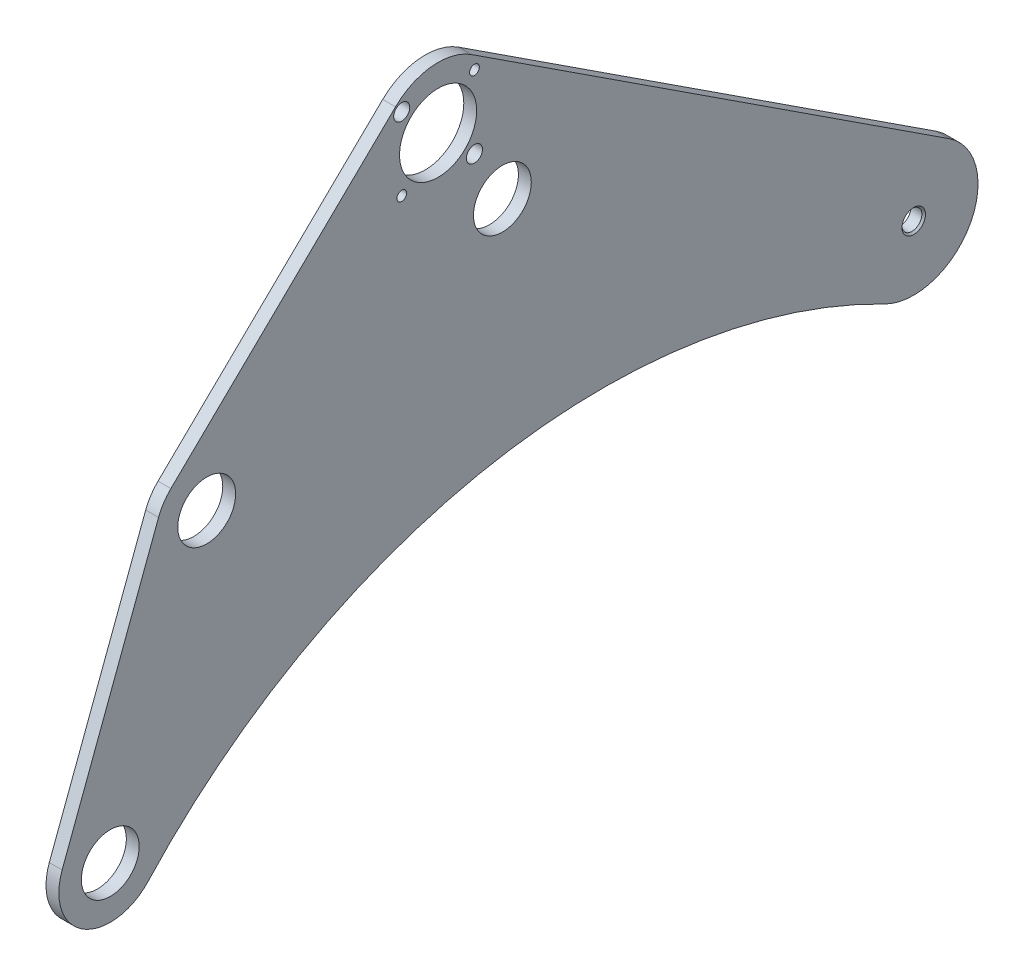
SolidWorks part; units mm, degrees
material "Acrylic (Medium-high impact)"
ref_plane "Front Plane" through (0, 0, 0) normal (0, 0, 1) x (1, 0, 0)
ref_plane "Top Plane" through (0, 0, 0) normal (0, 1, 0) x (1, 0, 0)
ref_plane "Right Plane" through (0, 0, 0) normal (1, 0, 0) x (0, 0, -1)
sketch "Sketch1" plane through (0, 0, 0) normal (1, 0, 0) x (0, 0, -1)
  line L0 (-548.7618, -304.8) -> (152.435, -304.8)
  line L1 (-192.8252, -101.6) -> (-152.4, -101.6)
  line L2 (-234.95, -143.7248) -> (-234.95, -186.4752)
  line L3 (-192.8252, -228.6) -> (-152.4, -228.6)
  line L4 (-152.4, -101.6) -> (-152.4, -228.6)
  circle A1 centre (0, 0) radius 6.35
  circle A6 centre (-396.875, -76.2) radius 9.525
  circle A7 centre (-349.25, 50.8) radius 9.525
  circle A8 centre (-203.2, 111.125) radius 9.525
  arc A9 (-234.95, -186.4752) -> (-192.8252, -228.6) centre (-192.8252, -186.4752) ccw
  arc A10 (-192.8252, -101.6) -> (-234.95, -143.7248) centre (-192.8252, -143.7248) ccw
  circle A11 centre (-192.8252, 12.7469) radius 120.65
  circle A12 centre (-234.95, 155.194) radius 29.845
  point P18 (-203.2, 17.7017)
  point P22 (-422.275, -186.4752)
  point P23 (-358.775, -82.55)
  point P24 (-358.775, -186.4752)
  point P25 (-221.0222, 10.8349)
  point P26 (-301.4265, -27.7432)
  point P27 (-192.8252, 12.7469)
  dimension "D1" = 12.7
  dimension "D2" = 19.05
  dimension "D3" = 42.1248
  dimension "D4" = 127
  dimension "D7" = 203.2
  dimension "D6" = 241.3
  dimension "D16" = 59.69
  dimension "D5" = 82.55
  dimension "D8" = 304.8
  dimension "D9" = 152.4
  dimension "D10" = 396.875
  dimension "D11" = 76.2
  dimension "D12" = 349.25
  dimension "D13" = 50.8
  dimension "D14" = 203.2
  dimension "D15" = 111.125
  dimension "D17" = 234.95
  dimension "D18" = 155.194
sketch "Sketch2" plane through (0, 0, 0) normal (1, 0, 0) x (0, 0, -1)
  line L1 (-420.6578, -67.2815) -> (-373.0328, 59.7185)
  line L3 (-366.9483, 69.0189) -> (-255.9667, 176.829)
  line L5 (-218.4679, 180.455) -> (17.3496, 26.5905)
  line L6 (-1001.8623, -101.6) -> (216.545, -101.6) construction
  line L7 (-1029.8132, 185.3565) -> (188.5941, 185.3565) construction
  arc A0 (-366.9483, 69.0189) -> (-373.0328, 59.7185) centre (-349.25, 50.8) ccw
  arc A2 (-420.6578, -67.2815) -> (-378.1608, -93.3738) centre (-396.875, -76.2) ccw
  arc A4 (-218.4679, 180.455) -> (-255.9667, 176.829) centre (-234.95, 155.194) ccw
  arc A5 (-14.4897, -28.2509) -> (17.3496, 26.5905) centre (0, 0) ccw
  arc A8 (-378.1608, -93.3738) -> (-14.4897, -28.2509) centre (-153.5905, -299.4593) cw
  circle A12 centre (-396.875, -76.2) radius 9.525 construction
  circle A13 centre (-349.25, 50.8) radius 9.525 construction
  dimension "D1" = 25.4
  dimension "D2" = 63.5
  dimension "D3" = 60.325
  dimension "D4" = 304.8
  dimension "D6" = 286.9565
extrude "Boss-Extrude1" add sketch "Sketch2" along normal blind 6.35
sketch "Sketch3" plane through (6.35, 0, 0) normal (1, 0, 0) x (0, 0, -1)
  line L0 (-216.9895, 173.1545) -> (-252.9105, 137.2335) construction
  line L1 (-234.95, 155.194) -> (-234.95, 205.0182) construction
  line L2 (-252.9105, 173.1545) -> (-216.9895, 137.2335) construction
  circle A0 centre (-203.2, 111.125) radius 14.2875
  circle A1 centre (-349.25, 50.8) radius 14.2875
  circle A2 centre (-396.875, -76.2) radius 14.2875
  circle A3 centre (-234.95, 155.194) radius 19.05
  circle A5 centre (-252.9105, 137.2335) radius 2.413
  circle A7 centre (-216.9895, 137.2335) radius 3.9687
  circle A8 centre (-216.9895, 173.1545) radius 2.413
  circle A9 centre (-252.9105, 173.1545) radius 3.9687
  point P18 (-234.95, 155.194)
  point P28 (-234.95, 155.194)
  dimension "D1" = 38.1
  dimension "D2" = 28.575
  dimension "D3" = 4.826
  dimension "D4" = 50.8
  dimension "D5" = 45
  dimension "D6" = 7.9375
  dimension "D7" = 50.8
extrude "Cut-Extrude1" cut sketch "Sketch3" against normal up to next
hole_wizard "3/8 Clearance Hole2" positions "Sketch7" profile "Sketch8" hole size "3/8" standard "ANSI Inch" end condition through all
sketch "Sketch7" plane through (6.35, 0, 0) normal (1, 0, 0) x (0, 0, -1)
  point P0 (0, 0)
sketch "Sketch8" plane through (6.35, 0, 0) normal (0, 1, 0) x (0, 0, -1)
  line L0 (0, 0) -> (0, 6.35)
  line L1 (0, 6.35) -> (4.9022, 6.35)
  line L2 (4.9022, 6.35) -> (4.9022, 0.8915)
  line L3 (4.9022, 0.8915) -> (5.7937, 0)
  line L5 (5.7937, 0) -> (0, 0)
  line L6 (-4.9022, 0.8915) -> (-5.7937, 0) construction
  line L11 (0, -6.35) -> (0, 107.95) construction
  dimension "Thru Hole Dia." = 9.8044
  dimension "Thru Hole Depth" = 6.35
  dimension "Near C'Sink Dia." = 11.5875
  dimension "Near C'Sink Angle" = 90
sketch "Sketch9" plane through (6.35, 0, 0) normal (1, 0, 0) x (0, 0, -1)
  line L0 (-495.9857, -101.6) -> (27.4607, -101.6) construction
  line L1 (100.4878, 185.3565) -> (-422.9585, 185.3565) construction
  arc A0 (-218.4679, 180.455) -> (-255.9667, 176.829) centre (-234.95, 155.194) ccw construction
  arc A1 (-420.6578, -67.2815) -> (-378.1608, -93.3738) centre (-396.875, -76.2) ccw construction
  dimension "D1" = 286.9565
